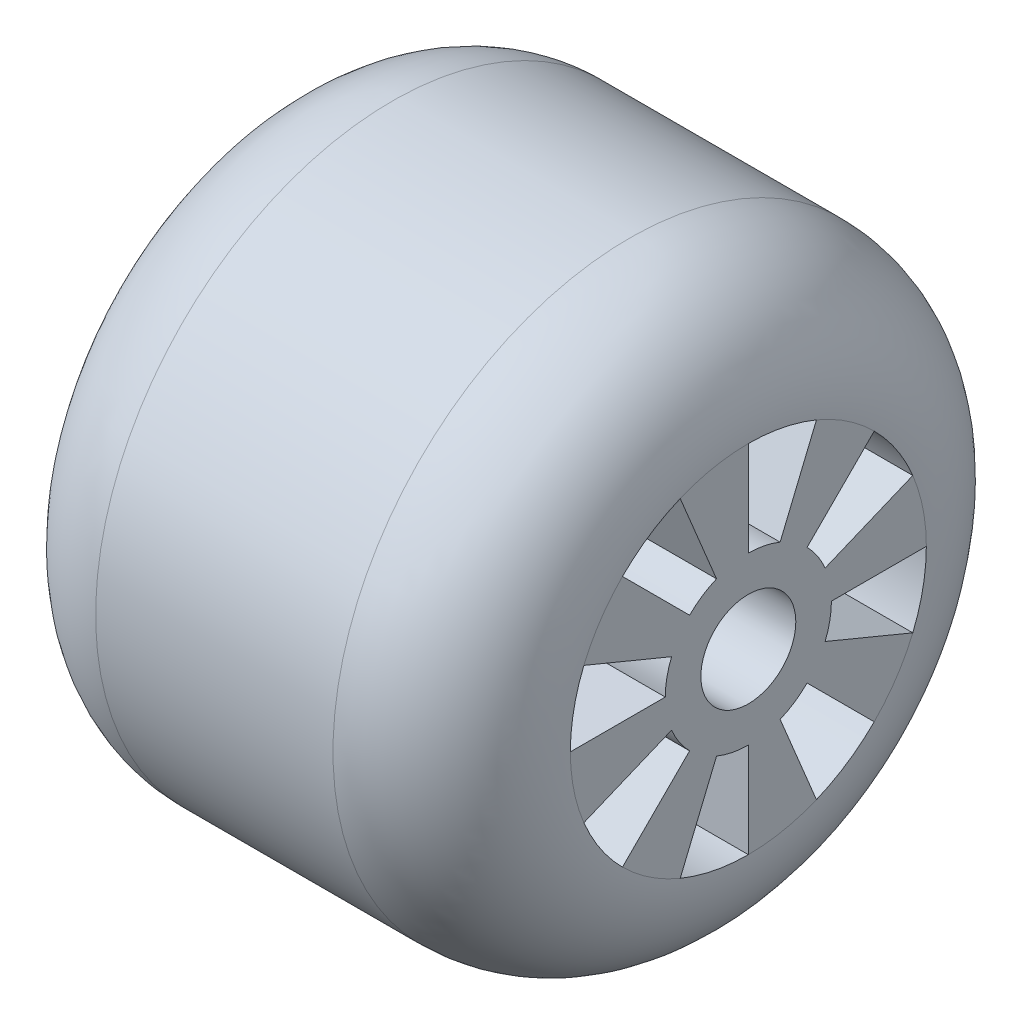
SolidWorks part; units mm, degrees
ref_plane "Front Plane" through (0, 0, 0) normal (0, 0, 1) x (1, 0, 0)
ref_plane "Top Plane" through (0, 0, 0) normal (0, 1, 0) x (1, 0, 0)
ref_plane "Right Plane" through (0, 0, 0) normal (1, 0, 0) x (0, 0, -1)
sketch "Sketch2" plane through (0, 0, 0) normal (1, 0, 0) x (0, 0, -1)
  line L0 (0, 7.5) -> (0, 3.5)
  line L1 (2.8701, 6.9291) -> (1.3394, 3.2336)
  line L2 (5.3033, 5.3033) -> (2.4749, 2.4749)
  line L3 (6.9291, 2.8701) -> (3.2336, 1.3394)
  line L4 (7.5, 0) -> (3.5, 0)
  line L5 (6.9291, -2.8701) -> (3.2336, -1.3394)
  line L6 (5.3033, -5.3033) -> (2.4749, -2.4749)
  line L7 (2.8701, -6.9291) -> (1.3394, -3.2336)
  line L8 (0, -7.5) -> (0, -3.5)
  line L9 (-2.8701, -6.9291) -> (-1.3394, -3.2336)
  line L10 (-5.3033, -5.3033) -> (-2.4749, -2.4749)
  line L11 (-6.9291, -2.8701) -> (-3.2336, -1.3394)
  line L12 (-7.5, 0) -> (-3.5, 0)
  line L13 (-6.9291, 2.8701) -> (-3.2336, 1.3394)
  line L14 (-5.3033, 5.3033) -> (-2.4749, 2.4749)
  line L15 (-2.8701, 6.9291) -> (-1.3394, 3.2336)
  circle A0 centre (0, 0) radius 12.5
  circle A1 centre (0, 0) radius 7.5
  circle A2 centre (0, 0) radius 3.5
  circle A3 centre (0, 0) radius 2
  point P40 (0, 0)
  dimension "D1" = 25
  dimension "D2" = 15
  dimension "D3" = 7
  dimension "D5" = 4
  dimension "D4" = 16
extrude "Boss-Extrude2" add sketch "Sketch2" along normal blind 20 contours A2 L5 A1 L4 | A2 L3 A1 L2 | A2 L1 A1 L0 | A2 L15 A1 L14 | A2 L13 A1 L12 | A2 L11 A1 L10 | A2 L9 A1 L8 | A2 L7 A1 L6 | A0 | A3 region at (0, 5.596, -1.1131) region at (0, 4.744, 3.1699) region at (0, 3.1699, -4.744) region at (0, 1.1131, 5.596) region at (0, -1.1131, -5.596) region at (0, -3.1699, 4.744) region at (0, -4.744, -3.1699) region at (0, -5.596, 1.1131)
fillet "Fillet2" radius 5 2 edges at (0, 0, -12.5) (20, 0, -12.5)
